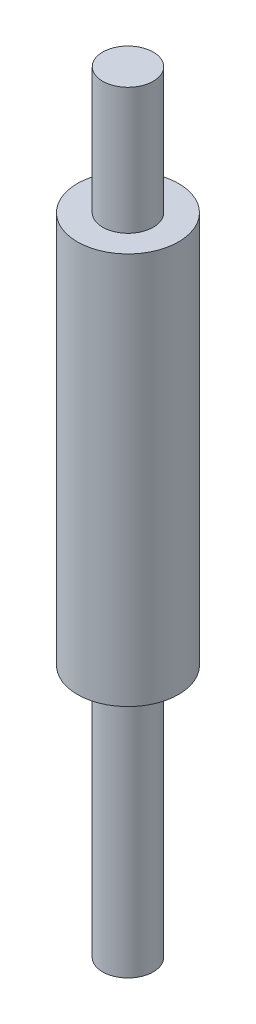
SolidWorks part; units mm, degrees
ref_plane "Front Plane" through (0, 0, 0) normal (0, 0, 1) x (1, 0, 0)
ref_plane "Top Plane" through (0, 0, 0) normal (0, 1, 0) x (1, 0, 0)
ref_plane "Right Plane" through (0, 0, 0) normal (1, 0, 0) x (0, 0, -1)
sketch "Sketch1" plane through (0, 0, 0) normal (0, 1, 0) x (1, 0, 0)
  circle A0 centre (0, 0) radius 4
  circle A1 centre (0, 0) radius 2
extrude "Boss-Extrude1" add sketch "Sketch1" along normal blind 31 contours A0 A1 | A1 region at (-3.8869, 0, 0) region at (0, 0, 0)
extrude "Boss-Extrude2" add sketch "Sketch1<4>" along normal blind 41 and the other way blind 20 contours A1 region at (0, 0, 0)
sketch "Sketch1<4>" plane through (0, 0, 0) normal (0, 1, 0) x (1, 0, 0) same geometry as "Sketch1"
